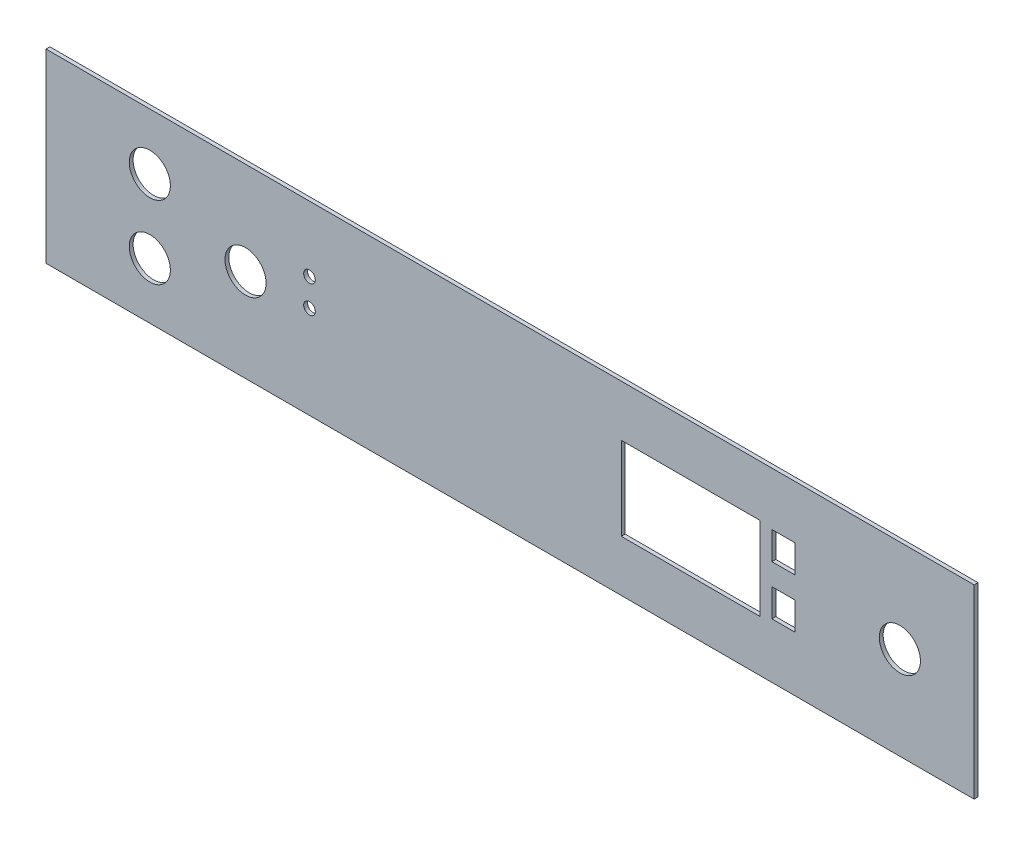
SolidWorks part; units mm, degrees
ref_plane "Front Plane" through (0, 0, 0) normal (0, 0, 1) x (1, 0, 0)
ref_plane "Top Plane" through (0, 0, 0) normal (0, 1, 0) x (1, 0, 0)
ref_plane "Right Plane" through (0, 0, 0) normal (1, 0, 0) x (0, 0, -1)
sketch "Sketch1" plane through (0, 0, 0) normal (0, 0, 1) x (1, 0, 0)
  line L1 (-254, 50.8) -> (254, 50.8)
  line L2 (-254, 50.8) -> (-254, -50.8)
  line L3 (-254, -50.8) -> (254, -50.8)
  line L4 (254, 50.8) -> (254, -50.8)
  line L5 (-254, 50.8) -> (254, -50.8) construction
  line L6 (-254, -50.8) -> (254, 50.8) construction
  point P0 (0, 0)
  dimension "D1" = 508
  dimension "D2" = 101.6
extrude "Front panel" add sketch "Sketch1" along normal blind 2.1
sketch "Sketch2" plane through (0, 0, 2.1) normal (0, 0, 1) x (1, 0, 0)
  line L0 (-197.1819, 20) -> (-197.1819, -20) construction
  circle A0 centre (-197.1819, 20) radius 11.25
  circle A1 centre (-197.1819, -20) radius 11.25
  point P4 (-197.1819, 0)
  dimension "D1" = 22.5
  dimension "D2" = 40
extrude "Start/stop" cut sketch "Sketch2" against normal through all
sketch "Sketch3" plane through (0, 0, 2.1) normal (0, 0, 1) x (1, 0, 0)
  line L0 (-197.1819, 20) -> (-197.1819, -20) construction
  circle A0 centre (-144.7898, 0) radius 11.25
  circle A1 centre (-109.7898, 15) radius 3.175
  circle A2 centre (-109.7898, 0) radius 3.175
  circle A3 centre (-197.1819, 20) radius 11.25 construction
  circle A4 centre (-197.1819, -20) radius 11.25 construction
  circle A5 centre (-197.1819, 20) radius 11.25 construction
  circle A6 centre (-197.1819, -20) radius 11.25 construction
  point P14 (-197.1819, 0)
  dimension "D1" = 6.35
  dimension "D2" = 22.5
  dimension "D3" = 35
  dimension "D4" = 15
extrude "Mode select" cut sketch "Sketch3" against normal through all
sketch "Sketch4" plane through (0, 0, 2.1) normal (0, 0, 1) x (1, 0, 0)
  line L0 (-197.1819, 20) -> (-197.1819, -20) construction
  line L1 (60.8601, 22.75) -> (136.8601, 22.75)
  line L2 (60.8601, 22.75) -> (60.8601, -22.75)
  line L3 (60.8601, -22.75) -> (136.8601, -22.75)
  line L4 (136.8601, 22.75) -> (136.8601, -22.75)
  line L5 (60.8601, 22.75) -> (136.8601, -22.75) construction
  line L6 (60.8601, -22.75) -> (136.8601, 22.75) construction
  circle A4 centre (-197.1819, -20) radius 11.25 construction
  circle A5 centre (-197.1819, -20) radius 11.25 construction
  point P0 (98.8601, 0)
  point P10 (-197.1819, 0)
  dimension "D1" = 45.5
  dimension "D2" = 76
extrude "LCD cutout" cut sketch "Sketch4" against normal through all
sketch "Sketch5" plane through (0, 0, 2.1) normal (0, 0, 1) x (1, 0, 0)
  circle A0 centre (213.3388, 0) radius 11.25
  point P4 (-144.7898, 0)
  dimension "D1" = 22.5
extrude "E-stop cutout" cut sketch "Sketch5" against normal through all
sketch "Sketch6" plane through (0, 0, 2.1) normal (0, 0, 1) x (1, 0, 0)
  line L0 (141.8601, -22.75) -> (159.8496, -22.75) construction
  line L1 (143.3201, 21.7025) -> (156.0201, 21.7025)
  line L2 (143.3201, 21.7025) -> (143.3201, 6.4625)
  line L3 (143.3201, 6.4625) -> (156.0201, 6.4625)
  line L4 (156.0201, 21.7025) -> (156.0201, 6.4625)
  line L5 (143.3201, 21.7025) -> (156.0201, 6.4625) construction
  line L6 (143.3201, 6.4625) -> (156.0201, 21.7025) construction
  line L7 (143.3201, -5.415) -> (156.0201, -5.415)
  line L8 (143.3201, -5.415) -> (143.3201, -20.655)
  line L9 (143.3201, -20.655) -> (156.0201, -20.655)
  line L10 (156.0201, -5.415) -> (156.0201, -20.655)
  line L11 (143.3201, -5.415) -> (156.0201, -20.655) construction
  line L12 (143.3201, -20.655) -> (156.0201, -5.415) construction
  line L13 (60.8601, -22.75) -> (136.8601, -22.75) construction
  line L14 (141.8601, 22.75) -> (158.6931, 22.75) construction
  line L15 (136.8601, 22.75) -> (60.8601, 22.75) construction
  line L16 (141.8601, 22.75) -> (141.8601, 20.3374) construction
  line L17 (141.8601, -22.75) -> (141.8601, 12.4166) construction
  line L18 (136.8601, -22.75) -> (136.8601, 22.75) construction
  point P0 (149.6701, 14.0825)
  point P5 (149.6701, -13.035)
  dimension "D1" = 15.24
  dimension "D2" = 12.7
  dimension "D3" = 2.095
  dimension "D4" = 2.095
  dimension "D5" = 1.46
  dimension "D6" = 1.46
  dimension "D7" = 5
extrude "LCD pushbuttons" cut sketch "Sketch6" against normal through all
